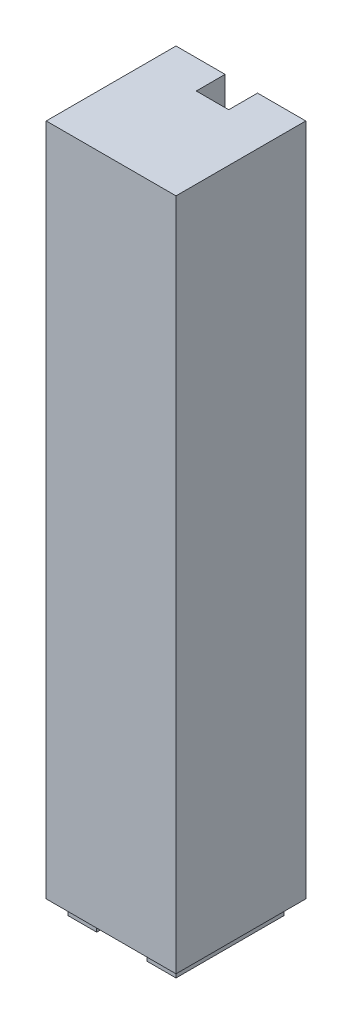
SolidWorks part; units mm, degrees
ref_plane "Front Plane" through (0, 0, 0) normal (0, 0, 1) x (1, 0, 0)
ref_plane "Top Plane" through (0, 0, 0) normal (0, 1, 0) x (1, 0, 0)
ref_plane "Right Plane" through (0, 0, 0) normal (1, 0, 0) x (0, 0, -1)
sketch "Sketch1" plane through (0, 0, 0) normal (0, 1, 0) x (1, 0, 0)
  line L1 (0, 0) -> (36, 0)
  line L2 (0, 0) -> (0, 36)
  line L3 (0, 36) -> (36, 36)
  line L4 (36, 0) -> (36, 36)
  dimension "D1" = 36
  dimension "D2" = 36
extrude "Boss-Extrude1" add sketch "Sketch1" along normal blind 186.9
sketch "Sketch2" plane through (0, 0, 0) normal (0, -1, 0) x (1, 0, 0)
  line L0 (0, 0) -> (36, 0) construction
  line L1 (3, -3) -> (7, -3)
  line L2 (3, -3) -> (3, -33)
  line L3 (3, -33) -> (7, -33)
  line L4 (7, -11) -> (7, -25)
  line L5 (36, -36) -> (0, -36) construction
  line L6 (0, -36) -> (0, 0) construction
  line L20 (36, 0) -> (36, -36) construction
  line L29 (7, -3) -> (11, -3)
  line L31 (7, -11) -> (11, -11)
  line L32 (11, -3) -> (11, -11)
  line L33 (7, -25) -> (11, -25)
  line L35 (7, -33) -> (11, -33)
  line L36 (11, -25) -> (11, -33)
  line L45 (29, -3) -> (33, -3)
  line L46 (29, -11) -> (29, -25)
  line L47 (29, -33) -> (33, -33)
  line L48 (33, -3) -> (33, -33)
  line L50 (29, -3) -> (25, -3)
  line L52 (29, -11) -> (25, -11)
  line L53 (25, -3) -> (25, -11)
  line L54 (29, -33) -> (25, -33)
  line L56 (29, -25) -> (25, -25)
  line L57 (25, -33) -> (25, -25)
  dimension "D1" = 3
  dimension "D2" = 3
  dimension "D3" = 3
  dimension "D4" = 4
  dimension "D5" = 4
  dimension "D6" = 8
  dimension "D7" = 8
  dimension "D8" = 4
  dimension "D9" = 3
  dimension "D10" = 3
  dimension "D11" = 3
  dimension "D12" = 4
  dimension "D13" = 4
  dimension "D14" = 4
extrude "Boss-Extrude2" add sketch "Sketch2" along normal blind 4
sketch "Sketch3" plane through (0, 0, 0) normal (0, -1, 0) x (1, 0, 0)
  line L0 (36, -36) -> (0, -36) construction
  line L2 (0, -36) -> (0, 0) construction
  circle A0 centre (18, -18) radius 2
  dimension "D1" = 4
  dimension "D2" = 18
  dimension "D3" = 18
extrude "Cut-Extrude1" cut sketch "Sketch3" against normal blind 5
sketch "Sketch4" plane through (0, 0, -36) normal (0, 0, 1) x (1, 0, 0)
  line L0 (0, 186.9) -> (36, 186.9) construction
  line L1 (13.62, 186.9) -> (22.62, 186.9)
  line L2 (13.62, 186.9) -> (13.62, 0)
  line L3 (13.62, 0) -> (22.62, 0)
  line L4 (22.62, 186.9) -> (22.62, 0)
  line L5 (0, 0) -> (36, 0) construction
  line L7 (36, 186.9) -> (36, 0) construction
  dimension "D1" = 13.38
  dimension "D2" = 9
extrude "Cut-Extrude2" cut sketch "Sketch4" along normal blind 8
